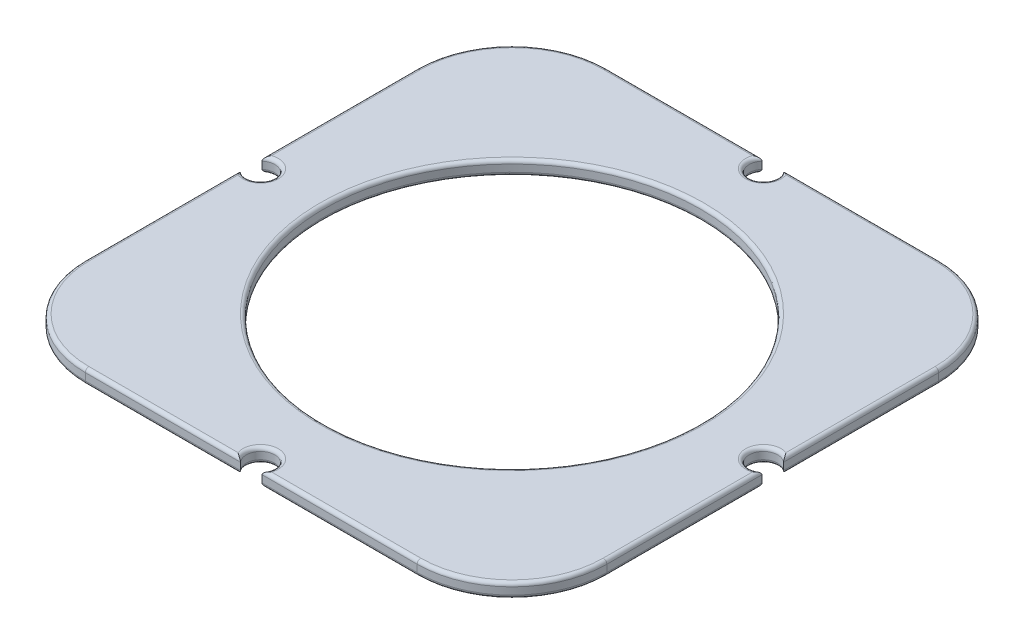
SolidWorks part; units mm, degrees
material "ABS"
ref_plane "Front Plane" through (0, 0, 0) normal (0, 0, 1) x (1, 0, 0)
ref_plane "Top Plane" through (0, 0, 0) normal (0, 1, 0) x (1, 0, 0)
ref_plane "Right Plane" through (0, 0, 0) normal (1, 0, 0) x (0, 0, -1)
sketch "Sketch1" plane through (0, 0, 0) normal (0, 1, 0) x (1, 0, 0)
  line L1 (-70, -110) -> (70, -110)
  line L2 (-110, -70) -> (-110, 70)
  line L3 (-70, 110) -> (70, 110)
  line L4 (110, -70) -> (110, 70)
  line L5 (-110, -110) -> (110, 110) construction
  line L6 (-110, 110) -> (110, -110) construction
  circle A1 centre (0, 0) radius 79.5
  arc A2 (-70, -110) -> (-110, -70) centre (-70, -70) cw
  circle A3 centre (0, 0) radius 87.5 construction
  arc A4 (70, -110) -> (110, -70) centre (70, -70) ccw
  arc A5 (70, 110) -> (110, 70) centre (70, 70) cw
  arc A6 (-110, 70) -> (-70, 110) centre (-70, 70) cw
  dimension "D1" = 220
  dimension "D2" = 8
  dimension "D3" = 40
extrude "Boss-Extrude1" add sketch "Sketch1" along normal blind 6
hole_wizard "CBORE for M10 SHCS" positions "Sketch2" profile "Sketch3" counterbore size "M10" standard "ANSI Metric" end condition through all
sketch "Sketch2" plane through (0, 21, 0) normal (0, 1, 0) x (1, 0, 0)
  line L1 (106.066, 0) -> (0, -106.066) construction
  line L2 (106.066, 0) -> (0, 106.066) construction
  line L3 (0, 106.066) -> (-106.066, 0) construction
  line L4 (0, -106.066) -> (-106.066, 0) construction
  line L5 (106.066, 0) -> (-106.066, 0) construction
  line L6 (0, 106.066) -> (0, -106.066) construction
  line L7 (-176.7767, 176.7767) -> (176.7767, 176.7767) construction
  line L8 (-176.7767, 176.7767) -> (-176.7767, -176.7767) construction
  line L9 (176.7767, 176.7767) -> (176.7767, -176.7767) construction
  line L10 (-176.7767, -176.7767) -> (176.7767, -176.7767) construction
  line L11 (-176.7767, 176.7767) -> (176.7767, -176.7767) construction
  line L12 (176.7767, 176.7767) -> (-176.7767, -176.7767) construction
  point P36 (0, 0)
  point P198 (-106.066, 0)
  point P201 (0, 106.066)
  point P204 (106.066, 0)
  point P207 (0, -106.066)
  point P210 (0, 0)
  point P341 (176.7767, 176.7767)
  point P344 (-176.7767, 176.7767)
  point P347 (176.7767, -176.7767)
  point P350 (-176.7767, -176.7767)
sketch "Sketch3" plane through (0, 21, 0) normal (1, 0, 0) x (0, 0, 1)
  line L0 (0, 0) -> (0, 21)
  line L1 (0, 21) -> (6, 21)
  line L2 (6, 21) -> (6, 10)
  line L3 (6, 10) -> (9, 10)
  line L4 (9, 10) -> (9, 0)
  line L5 (9, 0) -> (0, 0)
  line L6 (0, -6.35) -> (0, 107.95) construction
  dimension "Thru Hole Dia." = 12
  dimension "Thru Hole Depth" = 21
  dimension "C'Bore Dia." = 18
  dimension "C'Bore Depth" = 10
fillet "Fillet1" radius 1.5 34 edges at (0, 0, 79.5) (37.2652, 0, 110) (-37.2652, 0, 110) (98.2843, 0, 98.2843) (110, 0, -37.2652) (110, 0, 37.2652) (98.2843, 0, -98.2843) (-37.2652, 0, -110) (37.2652, 0, -110) (-98.2843, 0, -98.2843) (-110, 0, -37.2652) (-110, 0, 37.2652) (-98.2843, 0, 98.2843) (0, 6, 79.5) (-110, 6, -37.2652) (-110, 6, 37.2652) (-98.2843, 6, -98.2843) (37.2652, 6, -110) (-37.2652, 6, -110) (98.2843, 6, -98.2843) (110, 6, 37.2652) (110, 6, -37.2652) (98.2843, 6, 98.2843) (-37.2652, 6, 110) (37.2652, 6, 110) (-98.2843, 6, 98.2843) (0, 0, 100.066) (100.066, 0, 0) (0, 0, -100.066) (-100.066, 0, 0) (0, 6, 100.066) (100.066, 6, 0) (0, 6, -100.066) (-100.066, 6, 0)
